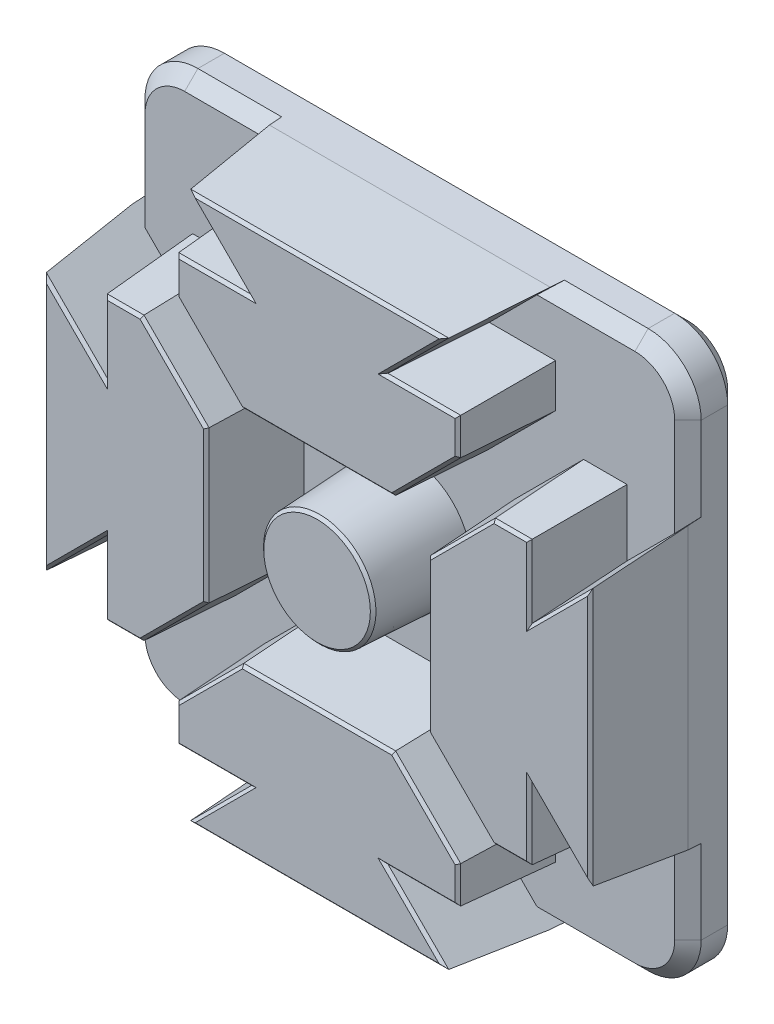
SolidWorks part; units mm, degrees
ref_plane "Plano frontal" through (0, 0, 0) normal (0, 0, 1) x (1, 0, 0)
ref_plane "Plano superior" through (0, 0, 0) normal (0, 1, 0) x (1, 0, 0)
ref_plane "Plano direito" through (0, 0, 0) normal (1, 0, 0) x (0, 0, -1)
sketch "Esboço1" plane through (0, 0, 0) normal (0, 0, 1) x (1, 0, 0)
  line L1 (-8.5, -10.5) -> (8.5, -10.5)
  line L2 (-10.5, -8.5) -> (-10.5, 8.5)
  line L3 (-8.5, 10.5) -> (8.5, 10.5)
  line L4 (10.5, -8.5) -> (10.5, 8.5)
  line L5 (-10.5, -10.5) -> (10.5, 10.5) construction
  line L6 (-10.5, 10.5) -> (10.5, -10.5) construction
  arc A0 (-8.5, -10.5) -> (-10.5, -8.5) centre (-8.5, -8.5) cw
  arc A1 (8.5, -10.5) -> (10.5, -8.5) centre (8.5, -8.5) ccw
  arc A2 (8.5, 10.5) -> (10.5, 8.5) centre (8.5, 8.5) cw
  arc A3 (-10.5, 8.5) -> (-8.5, 10.5) centre (-8.5, 8.5) cw
  point P0 (0, 0)
  dimension "D3" = 2
  dimension "D1" = 21
  dimension "D2" = 21
extrude "Ressalto-extrusão1" add sketch "Esboço1" along normal blind 2
sketch "Esboço2" plane through (0, 0, 0) normal (0, 0, -1) x (-1, 0, 0)
  line L56 (10, -9) -> (10, -4.8)
  line L57 (10, -4.8) -> (8.2, -3)
  line L58 (8.2, -3) -> (8.2, -5.5)
  line L59 (8.2, -5.5) -> (6.5607, -5.5)
  line L60 (6.5607, -5.5) -> (4, -2.9393)
  line L61 (4, -2.9393) -> (4, -0.3)
  line L62 (4, -0.3) -> (3.7, 0)
  line L63 (3.7, 0) -> (4, 0.3)
  line L64 (4, 0.3) -> (4, 2.9393)
  line L65 (4, 2.9393) -> (6.5607, 5.5)
  line L66 (6.5607, 5.5) -> (8.2, 5.5)
  line L67 (8.2, 5.5) -> (8.2, 3)
  line L68 (8.2, 3) -> (10, 4.8)
  line L69 (10, 4.8) -> (10, 9)
  line L70 (9, 10) -> (4.8, 10)
  line L71 (4.8, 10) -> (3, 8.2)
  line L72 (3, 8.2) -> (5.5, 8.2)
  line L73 (5.5, 8.2) -> (5.5, 6.5607)
  line L74 (5.5, 6.5607) -> (2.9393, 4)
  line L75 (2.9393, 4) -> (0.3, 4)
  line L76 (0.3, 4) -> (0, 3.7)
  line L77 (0, 3.7) -> (-0.3, 4)
  line L78 (-0.3, 4) -> (-2.9393, 4)
  line L79 (-2.9393, 4) -> (-5.5, 6.5607)
  line L80 (-5.5, 6.5607) -> (-5.5, 8.2)
  line L81 (-5.5, 8.2) -> (-3, 8.2)
  line L82 (-3, 8.2) -> (-4.8, 10)
  line L83 (-4.8, 10) -> (-9, 10)
  line L84 (-10, 9) -> (-10, 4.8)
  line L85 (-10, 4.8) -> (-8.2, 3)
  line L86 (-8.2, 3) -> (-8.2, 5.5)
  line L87 (-8.2, 5.5) -> (-6.5607, 5.5)
  line L88 (-6.5607, 5.5) -> (-4, 2.9393)
  line L89 (-4, 2.9393) -> (-4, 0.3)
  line L90 (-4, 0.3) -> (-3.7, 0)
  line L91 (-3.7, 0) -> (-4, -0.3)
  line L92 (-4, -0.3) -> (-4, -2.9393)
  line L93 (-4, -2.9393) -> (-6.5607, -5.5)
  line L94 (-6.5607, -5.5) -> (-8.2, -5.5)
  line L95 (-8.2, -5.5) -> (-8.2, -3)
  line L96 (-8.2, -3) -> (-10, -4.8)
  line L97 (-10, -4.8) -> (-10, -9)
  line L98 (-9, -10) -> (-4.8, -10)
  line L99 (-4.8, -10) -> (-3, -8.2)
  line L100 (-3, -8.2) -> (-5.5, -8.2)
  line L101 (-5.5, -8.2) -> (-5.5, -6.5607)
  line L102 (-5.5, -6.5607) -> (-2.9393, -4)
  line L103 (-2.9393, -4) -> (-0.3, -4)
  line L104 (-0.3, -4) -> (0, -3.7)
  line L105 (0, -3.7) -> (0.3, -4)
  line L106 (0.3, -4) -> (2.9393, -4)
  line L107 (2.9393, -4) -> (5.5, -6.5607)
  line L108 (5.5, -6.5607) -> (5.5, -8.2)
  line L109 (5.5, -8.2) -> (3, -8.2)
  line L110 (3, -8.2) -> (4.8, -10)
  line L111 (4.8, -10) -> (9, -10)
  line L112 (10, -9) -> (10, -4.8)
  line L113 (10, -4.8) -> (8.2, -3)
  line L114 (8.2, -3) -> (8.2, -5.5)
  line L115 (8.2, -5.5) -> (6.5607, -5.5)
  line L116 (6.5607, -5.5) -> (4, -2.9393)
  line L117 (4, -2.9393) -> (4, -0.3)
  line L118 (4, -0.3) -> (3.7, 0)
  line L119 (3.7, 0) -> (4, 0.3)
  line L120 (4, 0.3) -> (4, 2.9393)
  line L121 (4, 2.9393) -> (6.5607, 5.5)
  line L122 (6.5607, 5.5) -> (8.2, 5.5)
  line L123 (8.2, 5.5) -> (8.2, 3)
  line L124 (8.2, 3) -> (10, 4.8)
  line L125 (10, 4.8) -> (10, 9)
  line L126 (9, 10) -> (4.8, 10)
  line L127 (4.8, 10) -> (3, 8.2)
  line L128 (3, 8.2) -> (5.5, 8.2)
  line L129 (5.5, 8.2) -> (5.5, 6.5607)
  line L130 (5.5, 6.5607) -> (2.9393, 4)
  line L131 (2.9393, 4) -> (0.3, 4)
  line L132 (0.3, 4) -> (0, 3.7)
  line L133 (0, 3.7) -> (-0.3, 4)
  line L134 (-0.3, 4) -> (-2.9393, 4)
  line L135 (-2.9393, 4) -> (-5.5, 6.5607)
  line L136 (-5.5, 6.5607) -> (-5.5, 8.2)
  line L137 (-5.5, 8.2) -> (-3, 8.2)
  line L138 (-3, 8.2) -> (-4.8, 10)
  line L139 (-4.8, 10) -> (-9, 10)
  line L140 (-10, 9) -> (-10, 4.8)
  line L141 (-10, 4.8) -> (-8.2, 3)
  line L142 (-8.2, 3) -> (-8.2, 5.5)
  line L143 (-8.2, 5.5) -> (-6.5607, 5.5)
  line L144 (-6.5607, 5.5) -> (-4, 2.9393)
  line L145 (-4, 2.9393) -> (-4, 0.3)
  line L146 (-4, 0.3) -> (-3.7, 0)
  line L147 (-3.7, 0) -> (-4, -0.3)
  line L148 (-4, -0.3) -> (-4, -2.9393)
  line L149 (-4, -2.9393) -> (-6.5607, -5.5)
  line L150 (-6.5607, -5.5) -> (-8.2, -5.5)
  line L151 (-8.2, -5.5) -> (-8.2, -3)
  line L152 (-8.2, -3) -> (-10, -4.8)
  line L153 (-10, -4.8) -> (-10, -9)
  line L154 (-9, -10) -> (-4.8, -10)
  line L155 (-4.8, -10) -> (-3, -8.2)
  line L156 (-3, -8.2) -> (-5.5, -8.2)
  line L157 (-5.5, -8.2) -> (-5.5, -6.5607)
  line L158 (-5.5, -6.5607) -> (-2.9393, -4)
  line L159 (-2.9393, -4) -> (-0.3, -4)
  line L160 (-0.3, -4) -> (0, -3.7)
  line L161 (0, -3.7) -> (0.3, -4)
  line L162 (0.3, -4) -> (2.9393, -4)
  line L163 (2.9393, -4) -> (5.5, -6.5607)
  line L164 (5.5, -6.5607) -> (5.5, -8.2)
  line L165 (5.5, -8.2) -> (3, -8.2)
  line L166 (3, -8.2) -> (4.8, -10)
  line L167 (4.8, -10) -> (9, -10)
  circle A0 centre (0, 0) radius 2.3 construction
  circle A1 centre (0, 0) radius 2.3
  arc A4 (9, -10) -> (10, -9) centre (9, -9) ccw
  arc A5 (10, 9) -> (9, 10) centre (9, 9) ccw
  arc A6 (-9, 10) -> (-10, 9) centre (-9, 9) ccw
  arc A7 (-10, -9) -> (-9, -10) centre (-9, -9) ccw
  arc A8 (9, -10) -> (10, -9) centre (9, -9) ccw
  arc A9 (10, 9) -> (9, 10) centre (9, 9) ccw
  arc A10 (-9, 10) -> (-10, 9) centre (-9, 9) ccw
  arc A11 (-10, -9) -> (-9, -10) centre (-9, -9) ccw
  dimension "D1" = 0
sketch "Esboço3" plane through (0, 0, 2) normal (0, 0, 1) x (1, 0, 0)
  line L56 (-8.5, -10.5) -> (8.5, -10.5) construction
  line L57 (-10.5, 8.5) -> (-10.5, -8.5) construction
  line L58 (8.5, 10.5) -> (-8.5, 10.5) construction
  line L59 (10.5, -8.5) -> (10.5, 8.5) construction
  line L60 (-5.0879, 10.5) -> (5.0879, 10.5)
  line L61 (10.5, 5.0879) -> (10.5, -5.0879)
  line L62 (5.0879, -10.5) -> (-5.0879, -10.5)
  line L63 (-10.5, -5.0879) -> (-10.5, 5.0879)
  line L112 (-4.15, 2.8772) -> (-4.15, 0.2379)
  line L113 (-4.15, 0.2379) -> (-3.9121, 0)
  line L114 (-3.9121, 0) -> (-4.15, -0.2379)
  line L115 (-4.15, -0.2379) -> (-4.15, -2.8772)
  line L116 (-4.15, -2.8772) -> (-6.6228, -5.35)
  line L117 (-6.6228, -5.35) -> (-8.05, -5.35)
  line L118 (-8.05, -5.35) -> (-8.05, -2.6379)
  line L119 (-8.05, -2.6379) -> (-10.15, -4.7379)
  line L120 (-10.15, -4.7379) -> (-10.15, -9)
  line L121 (-9, -10.15) -> (-4.7379, -10.15)
  line L122 (-4.7379, -10.15) -> (-2.6379, -8.05)
  line L123 (-2.6379, -8.05) -> (-5.35, -8.05)
  line L124 (-5.35, -8.05) -> (-5.35, -6.6228)
  line L125 (-5.35, -6.6228) -> (-2.8772, -4.15)
  line L126 (-2.8772, -4.15) -> (-0.2379, -4.15)
  line L127 (-0.2379, -4.15) -> (0, -3.9121)
  line L128 (0, -3.9121) -> (0.2379, -4.15)
  line L129 (0.2379, -4.15) -> (2.8772, -4.15)
  line L130 (2.8772, -4.15) -> (5.35, -6.6228)
  line L131 (5.35, -6.6228) -> (5.35, -8.05)
  line L132 (5.35, -8.05) -> (2.6379, -8.05)
  line L133 (2.6379, -8.05) -> (4.7379, -10.15)
  line L134 (4.7379, -10.15) -> (9, -10.15)
  line L135 (10.15, -9) -> (10.15, -4.7379)
  line L136 (10.15, -4.7379) -> (8.05, -2.6379)
  line L137 (8.05, -2.6379) -> (8.05, -5.35)
  line L138 (8.05, -5.35) -> (6.6228, -5.35)
  line L139 (6.6228, -5.35) -> (4.15, -2.8772)
  line L140 (4.15, -2.8772) -> (4.15, -0.2379)
  line L141 (4.15, -0.2379) -> (3.9121, 0)
  line L142 (3.9121, 0) -> (4.15, 0.2379)
  line L143 (4.15, 0.2379) -> (4.15, 2.8772)
  line L144 (4.15, 2.8772) -> (6.6228, 5.35)
  line L145 (6.6228, 5.35) -> (8.05, 5.35)
  line L146 (8.05, 5.35) -> (8.05, 2.6379)
  line L147 (8.05, 2.6379) -> (10.15, 4.7379)
  line L148 (10.15, 4.7379) -> (10.15, 9)
  line L149 (9, 10.15) -> (4.7379, 10.15)
  line L150 (4.7379, 10.15) -> (2.6379, 8.05)
  line L151 (2.6379, 8.05) -> (5.35, 8.05)
  line L152 (5.35, 8.05) -> (5.35, 6.6228)
  line L153 (5.35, 6.6228) -> (2.8772, 4.15)
  line L154 (2.8772, 4.15) -> (0.2379, 4.15)
  line L155 (0.2379, 4.15) -> (0, 3.9121)
  line L156 (0, 3.9121) -> (-0.2379, 4.15)
  line L157 (-0.2379, 4.15) -> (-2.8772, 4.15)
  line L158 (-2.8772, 4.15) -> (-5.35, 6.6228)
  line L159 (-5.35, 6.6228) -> (-5.35, 8.05)
  line L160 (-5.35, 8.05) -> (-2.6379, 8.05)
  line L161 (-2.6379, 8.05) -> (-4.7379, 10.15)
  line L162 (-4.7379, 10.15) -> (-9, 10.15)
  line L163 (-10.15, 9) -> (-10.15, 4.7379)
  line L164 (-10.15, 4.7379) -> (-8.05, 2.6379)
  line L165 (-8.05, 2.6379) -> (-8.05, 5.35)
  line L166 (-8.05, 5.35) -> (-6.6228, 5.35)
  line L167 (-6.6228, 5.35) -> (-4.15, 2.8772)
  line L168 (-4.15, 2.8772) -> (-4.15, 0.2379)
  line L171 (-4.15, 0.2379) -> (-4.15, -2.8772)
  line L172 (-4.15, -2.8772) -> (-6.6228, -5.35)
  line L173 (-6.6228, -5.35) -> (-8.05, -5.35)
  line L174 (-8.05, -5.35) -> (-8.05, -2.6379)
  line L175 (-8.05, -2.6379) -> (-10.5, -5.0879)
  line L178 (-5.0879, -10.5) -> (-2.6379, -8.05)
  line L179 (-2.6379, -8.05) -> (-5.35, -8.05)
  line L180 (-5.35, -8.05) -> (-5.35, -6.6228)
  line L181 (-5.35, -6.6228) -> (-2.8772, -4.15)
  line L182 (-2.8772, -4.15) -> (-0.2379, -4.15)
  line L185 (-0.2379, -4.15) -> (2.8772, -4.15)
  line L186 (2.8772, -4.15) -> (5.35, -6.6228)
  line L187 (5.35, -6.6228) -> (5.35, -8.05)
  line L188 (5.35, -8.05) -> (2.6379, -8.05)
  line L189 (2.6379, -8.05) -> (5.0879, -10.5)
  line L192 (10.5, -5.0879) -> (8.05, -2.6379)
  line L193 (8.05, -2.6379) -> (8.05, -5.35)
  line L194 (8.05, -5.35) -> (6.6228, -5.35)
  line L195 (6.6228, -5.35) -> (4.15, -2.8772)
  line L196 (4.15, -2.8772) -> (4.15, -0.2379)
  line L199 (4.15, -0.2379) -> (4.15, 2.8772)
  line L200 (4.15, 2.8772) -> (6.6228, 5.35)
  line L201 (6.6228, 5.35) -> (8.05, 5.35)
  line L202 (8.05, 5.35) -> (8.05, 2.6379)
  line L203 (8.05, 2.6379) -> (10.5, 5.0879)
  line L206 (5.0879, 10.5) -> (2.6379, 8.05)
  line L207 (2.6379, 8.05) -> (5.35, 8.05)
  line L208 (5.35, 8.05) -> (5.35, 6.6228)
  line L209 (5.35, 6.6228) -> (2.8772, 4.15)
  line L210 (2.8772, 4.15) -> (0.2379, 4.15)
  line L213 (0.2379, 4.15) -> (-2.8772, 4.15)
  line L214 (-2.8772, 4.15) -> (-5.35, 6.6228)
  line L215 (-5.35, 6.6228) -> (-5.35, 8.05)
  line L216 (-5.35, 8.05) -> (-2.6379, 8.05)
  line L217 (-2.6379, 8.05) -> (-5.0879, 10.5)
  line L220 (-10.5, 5.0879) -> (-8.05, 2.6379)
  line L221 (-8.05, 2.6379) -> (-8.05, 5.35)
  line L222 (-8.05, 5.35) -> (-6.6228, 5.35)
  line L223 (-6.6228, 5.35) -> (-4.15, 2.8772)
  circle A6 centre (0, 0) radius 2.15
  circle A7 centre (0, 0) radius 2.15
  arc A8 (-10.15, -9) -> (-9, -10.15) centre (-9, -9) ccw
  arc A9 (9, -10.15) -> (10.15, -9) centre (9, -9) ccw
  arc A10 (10.15, 9) -> (9, 10.15) centre (9, 9) ccw
  arc A11 (-9, 10.15) -> (-10.15, 9) centre (-9, 9) ccw
  dimension "D1" = 0.15
  dimension "D2" = 0.15
sketch "Esboço4" plane through (0, 0, 2) normal (0, 0, 1) x (1, 0, 0)
  line L0 (-10.5, 8.5) -> (-10.5, -8.5) construction
  line L1 (8.5, 10.5) -> (-8.5, 10.5) construction
  line L2 (10.5, -8.5) -> (10.5, 8.5) construction
  line L3 (-8.5, -10.5) -> (8.5, -10.5) construction
  line L4 (-5.3, 10.5) -> (5.3, 10.5)
  line L5 (10.5, 5.3) -> (10.5, -5.3)
  line L6 (5.3, -10.5) -> (-5.3, -10.5)
  line L7 (-10.5, -5.3) -> (-10.5, 5.3)
  line L56 (-5.5, -6.5607) -> (-2.9393, -4)
  line L57 (-5.5, -8.2) -> (-5.5, -6.5607)
  line L58 (-3, -8.2) -> (-5.5, -8.2)
  line L59 (-4.8, -10) -> (-3, -8.2)
  line L60 (-9, -10) -> (-4.8, -10)
  line L61 (-10, -4.8) -> (-10, -9)
  line L62 (-8.2, -3) -> (-10, -4.8)
  line L63 (-8.2, -5.5) -> (-8.2, -3)
  line L64 (-6.5607, -5.5) -> (-8.2, -5.5)
  line L65 (-4, -2.9393) -> (-6.5607, -5.5)
  line L66 (-4, -0.3) -> (-4, -2.9393)
  line L67 (-3.7, 0) -> (-4, -0.3)
  line L68 (-4, 0.3) -> (-3.7, 0)
  line L69 (-4, 2.9393) -> (-4, 0.3)
  line L70 (-6.5607, 5.5) -> (-4, 2.9393)
  line L71 (-8.2, 5.5) -> (-6.5607, 5.5)
  line L72 (-8.2, 3) -> (-8.2, 5.5)
  line L73 (-10, 4.8) -> (-8.2, 3)
  line L74 (-10, 9) -> (-10, 4.8)
  line L75 (-4.8, 10) -> (-9, 10)
  line L76 (-3, 8.2) -> (-4.8, 10)
  line L77 (-5.5, 8.2) -> (-3, 8.2)
  line L78 (-5.5, 6.5607) -> (-5.5, 8.2)
  line L79 (-2.9393, 4) -> (-5.5, 6.5607)
  line L80 (-0.3, 4) -> (-2.9393, 4)
  line L81 (0, 3.7) -> (-0.3, 4)
  line L82 (0.3, 4) -> (0, 3.7)
  line L83 (2.9393, 4) -> (0.3, 4)
  line L84 (5.5, 6.5607) -> (2.9393, 4)
  line L85 (5.5, 8.2) -> (5.5, 6.5607)
  line L86 (3, 8.2) -> (5.5, 8.2)
  line L87 (4.8, 10) -> (3, 8.2)
  line L88 (9, 10) -> (4.8, 10)
  line L89 (10, 4.8) -> (10, 9)
  line L90 (8.2, 3) -> (10, 4.8)
  line L91 (8.2, 5.5) -> (8.2, 3)
  line L92 (6.5607, 5.5) -> (8.2, 5.5)
  line L93 (4, 2.9393) -> (6.5607, 5.5)
  line L94 (4, 0.3) -> (4, 2.9393)
  line L95 (3.7, 0) -> (4, 0.3)
  line L96 (4, -0.3) -> (3.7, 0)
  line L97 (4, -2.9393) -> (4, -0.3)
  line L98 (6.5607, -5.5) -> (4, -2.9393)
  line L99 (8.2, -5.5) -> (6.5607, -5.5)
  line L100 (8.2, -3) -> (8.2, -5.5)
  line L101 (10, -4.8) -> (8.2, -3)
  line L102 (10, -9) -> (10, -4.8)
  line L103 (4.8, -10) -> (9, -10)
  line L104 (3, -8.2) -> (4.8, -10)
  line L105 (5.5, -8.2) -> (3, -8.2)
  line L106 (5.5, -6.5607) -> (5.5, -8.2)
  line L107 (2.9393, -4) -> (5.5, -6.5607)
  line L108 (0.3, -4) -> (2.9393, -4)
  line L109 (0, -3.7) -> (0.3, -4)
  line L110 (-0.3, -4) -> (0, -3.7)
  line L111 (-2.9393, -4) -> (-0.3, -4)
  line L112 (-5.5, -6.5607) -> (-2.9393, -4)
  line L113 (-5.5, -8.2) -> (-5.5, -6.5607)
  line L114 (-3, -8.2) -> (-5.5, -8.2)
  line L115 (-5.3, -10.5) -> (-3, -8.2)
  line L118 (-8.2, -3) -> (-10.5, -5.3)
  line L119 (-8.2, -5.5) -> (-8.2, -3)
  line L120 (-6.5607, -5.5) -> (-8.2, -5.5)
  line L121 (-4, -2.9393) -> (-6.5607, -5.5)
  line L122 (-4, 0.3) -> (-4, -2.9393)
  line L125 (-4, 2.9393) -> (-4, 0.3)
  line L126 (-6.5607, 5.5) -> (-4, 2.9393)
  line L127 (-8.2, 5.5) -> (-6.5607, 5.5)
  line L128 (-8.2, 3) -> (-8.2, 5.5)
  line L129 (-10.5, 5.3) -> (-8.2, 3)
  line L132 (-3, 8.2) -> (-5.3, 10.5)
  line L133 (-5.5, 8.2) -> (-3, 8.2)
  line L134 (-5.5, 6.5607) -> (-5.5, 8.2)
  line L135 (-2.9393, 4) -> (-5.5, 6.5607)
  line L136 (0.3, 4) -> (-2.9393, 4)
  line L139 (2.9393, 4) -> (0.3, 4)
  line L140 (5.5, 6.5607) -> (2.9393, 4)
  line L141 (5.5, 8.2) -> (5.5, 6.5607)
  line L142 (3, 8.2) -> (5.5, 8.2)
  line L143 (5.3, 10.5) -> (3, 8.2)
  line L146 (8.2, 3) -> (10.5, 5.3)
  line L147 (8.2, 5.5) -> (8.2, 3)
  line L148 (6.5607, 5.5) -> (8.2, 5.5)
  line L149 (4, 2.9393) -> (6.5607, 5.5)
  line L150 (4, -0.3) -> (4, 2.9393)
  line L153 (4, -2.9393) -> (4, -0.3)
  line L154 (6.5607, -5.5) -> (4, -2.9393)
  line L155 (8.2, -5.5) -> (6.5607, -5.5)
  line L156 (8.2, -3) -> (8.2, -5.5)
  line L157 (10.5, -5.3) -> (8.2, -3)
  line L160 (3, -8.2) -> (5.3, -10.5)
  line L161 (5.5, -8.2) -> (3, -8.2)
  line L162 (5.5, -6.5607) -> (5.5, -8.2)
  line L163 (2.9393, -4) -> (5.5, -6.5607)
  line L164 (-0.3, -4) -> (2.9393, -4)
  line L167 (-2.9393, -4) -> (-0.3, -4)
  circle A1 centre (0, 0) radius 2.3
  circle A2 centre (0, 0) radius 2.3
  arc A6 (-10, -9) -> (-9, -10) centre (-9, -9) ccw
  arc A7 (-9, 10) -> (-10, 9) centre (-9, 9) ccw
  arc A8 (10, 9) -> (9, 10) centre (9, 9) ccw
  arc A9 (9, -10) -> (10, -9) centre (9, -9) ccw
  dimension "D1" = 0
  dimension "D2" = 0
extrude "Ressalto-extrusão2" add sketch "Esboço4" along normal blind 3.5 draft 3
chamfer "Chanfro1" distance 0.5 angle 45 20 edges at (-6.9, 10.5, 2) (-10.5, 6.9, 2) (-9.9142, 9.9142, 2) (10.5, 6.9, 2) (6.9, 10.5, 2) (9.9142, 9.9142, 2) (6.9, -10.5, 2) (10.5, -6.9, 2) (9.9142, -9.9142, 2) (-10.5, -6.9, 2) (-6.9, -10.5, 2) (-9.9142, -9.9142, 2) (0, 10.5, 0) (-9.9142, 9.9142, 0) (9.9142, 9.9142, 0) (-10.5, 0, 0) (10.5, 0, 0) (-9.9142, -9.9142, 0) (9.9142, -9.9142, 0) (0, -10.5, 0)
chamfer "Chanfro2" distance 0.1 angle 45 41 edges at (2.1166, 0, 5.5) (10.3166, 0, 5.5) (9.1666, -3.7072, 5.5) (8.0166, -3.9369, 5.5) (7.3266, -5.3166, 5.5) (5.41, -4.09, 5.5) (4.1834, 0, 5.5) (5.41, 4.09, 5.5) (7.3266, 5.3166, 5.5) (8.0166, 3.9369, 5.5) (9.1666, 3.7072, 5.5) (0, 10.3166, 5.5) (3.7072, 9.1666, 5.5) (3.9369, 8.0166, 5.5) (5.3166, 7.3266, 5.5) (4.09, 5.41, 5.5) (0, 4.1834, 5.5) (-4.09, 5.41, 5.5) (-5.3166, 7.3266, 5.5) (-3.9369, 8.0166, 5.5) (-3.7072, 9.1666, 5.5) (-10.3166, 0, 5.5) (-9.1666, 3.7072, 5.5) (-8.0166, 3.9369, 5.5) (-7.3266, 5.3166, 5.5) (-5.41, 4.09, 5.5) (-4.1834, 0, 5.5) (-5.41, -4.09, 5.5) (-7.3266, -5.3166, 5.5) (-8.0166, -3.9369, 5.5) (-9.1666, -3.7072, 5.5) (4.09, -5.41, 5.5) (5.3166, -7.3266, 5.5) (3.9369, -8.0166, 5.5) (3.7072, -9.1666, 5.5) (0, -10.3166, 5.5) (-3.7072, -9.1666, 5.5) (-3.9369, -8.0166, 5.5) (-5.3166, -7.3266, 5.5) (-4.09, -5.41, 5.5) (0, -4.1834, 5.5)
